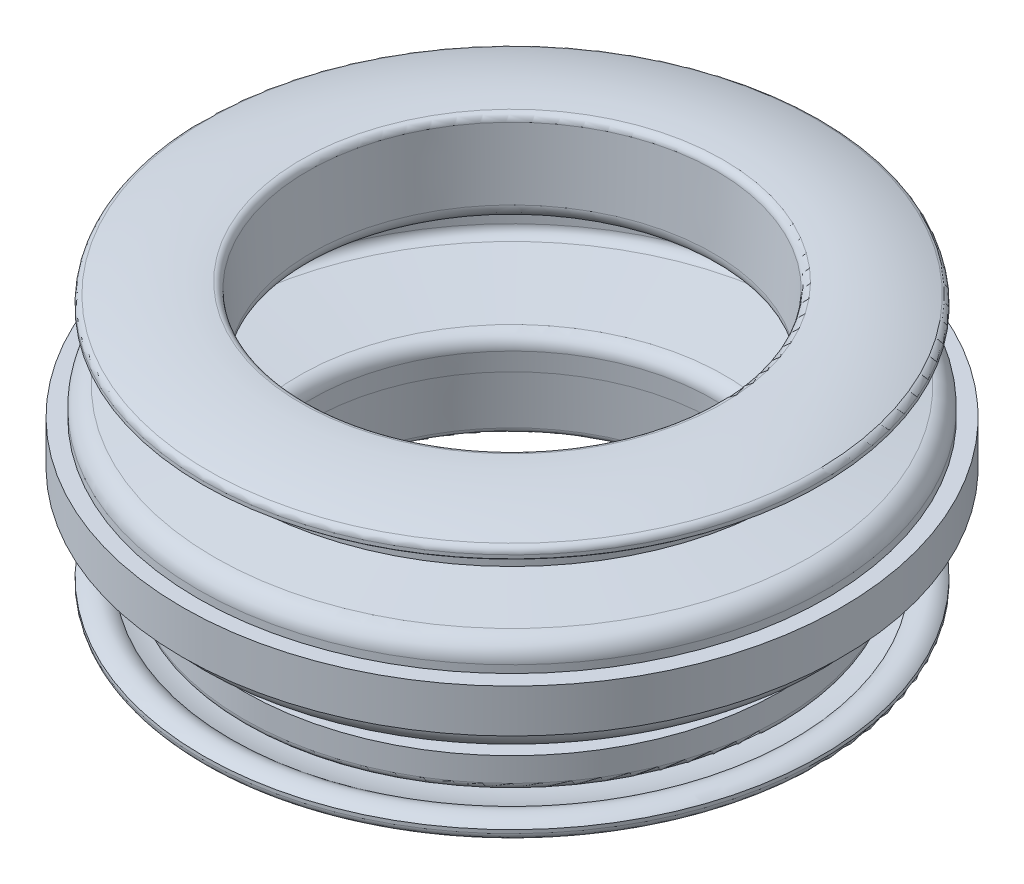
SolidWorks part; units mm, degrees
ref_plane "Front Plane" through (0, 0, 0) normal (0, 0, 1) x (1, 0, 0)
ref_plane "Top Plane" through (0, 0, 0) normal (0, 1, 0) x (1, 0, 0)
ref_plane "Right Plane" through (0, 0, 0) normal (1, 0, 0) x (0, 0, -1)
ref_plane "Plane2" through (0, -4.572, 0) normal (0, 1, 0) x (1, 0, 0)
ref_plane "Plane4" through (0, -45.212, 0) normal (0, 1, 0) x (1, 0, 0)
ref_plane "Plane3" through (0, -24.892, 0) normal (0, 1, 0) x (1, 0, 0)
sketch "Sketch1" plane through (0, 0, 0) normal (0, 0, 1) x (1, 0, 0)
  line L0 (0, 0) -> (0, 51.7671) construction
  line L1 (36.83, 0) -> (36.83, -10.16)
  line L4 (36.83, -10.16) -> (48.26, -10.16)
  line L5 (48.26, -10.16) -> (48.26, -4.572)
  line L6 (48.26, -4.572) -> (43.0459, -4.572)
  line L11 (44.2545, -3.556) -> (39.5655, -3.556) construction
  line L12 (55.5625, -2.286) -> (55.5625, -3.81)
  line L13 (43.0459, -2.54) -> (27.2208, -2.54) construction
  arc A0 (36.83, 0) -> (55.5625, -2.286) centre (41.2472, -41.6979) cw
  arc A1 (43.0459, -2.54) -> (43.0459, -4.572) centre (41.91, -3.556) ccw
  arc A2 (55.5625, -3.81) -> (50.4825, -3.81) centre (53.0225, -0.9702) cw
  arc A3 (43.0459, -2.54) -> (50.4825, -3.81) centre (43.0459, -24.9477) cw
  point P23 (41.91, -3.556)
  dimension "D1" = 73.66
  dimension "D5" = 1.524
  dimension "D2" = 2.032
  dimension "D10" = 41.9312
  dimension "D14" = 3.81
  dimension "D15" = 1.524
  dimension "D3" = 5.08
  dimension "D4" = 96.52
  dimension "D8" = 83.82
  dimension "D9" = 3.556
  dimension "D11" = 111.125
  dimension "D12" = 10.16
  dimension "D16" = 0.762
revolve "Revolve1" add sketch "Sketch1" angle 360 about L0
draft "Draft1" type of draft neutral plane draft angle 3 neutral plane "Top Plane" faces to draft 1 face at (0, -10.16, -36.83) neutral plane through (0, 0, 0) neutral plane normal (0, 1, 0) parameters "D1"=3
fillet "Fillet3" radius 1.27 1 edges at (0, 0, -36.83)
fillet "Fillet4" radius 1.27 1 edges at (0, -2.286, -55.5625)
fillet "Fillet5" radius 1.27 1 edges at (0, -4.572, -48.26)
mirror "Mirror4" about plane through (0, -24.892, 0) normal (0, 1, 0) of bodies 101
sketch "Sketch2" plane through (0, 0, 0) normal (0, 0, 1) x (1, 0, 0)
  line L0 (61.1187, -24.892) -> (-61.1187, -24.892) construction
  line L1 (-59.2604, -24.892) -> (-54.5176, -24.892)
  line L2 (-59.2604, -24.892) -> (-59.2604, -21.0052)
  line L4 (-54.5176, -24.892) -> (-54.5176, -21.0052)
  line L5 (0, 0) -> (0, -56.0151) construction
  line L6 (-54.5176, -21.0052) -> (-54.5176, -20.3326)
  line L7 (-53.0528, -18.6056) -> (-38.2434, -16.1545)
  line L8 (-36.1217, -13.5156) -> (-36.2975, -10.16)
  line L9 (-48.26, -10.16) -> (48.26, -10.16) construction
  line L10 (-36.2975, -10.16) -> (-38.8375, -10.16)
  line L11 (-38.8375, -10.16) -> (-38.8375, -12.0626)
  line L12 (-40.4315, -13.9421) -> (-53.4992, -16.1049)
  line L13 (-56.4949, -19.6371) -> (-56.4949, -21.0052)
  line L15 (-56.4949, -21.0052) -> (-59.2604, -21.0052)
  line L17 (-36.2975, -10.16) -> (36.2975, -10.16) construction
  line L18 (-36.7725, -1.0968) -> (-36.2975, -10.16) construction
  line L19 (-36.7725, -1.0968) -> (36.7725, -1.0968) construction
  arc A0 (-54.5176, -20.3326) -> (-53.0528, -18.6056) centre (-52.767, -20.3326) cw
  arc A1 (-53.4992, -16.1049) -> (-56.4949, -19.6371) centre (-52.9146, -19.6371) ccw
  arc A2 (-38.2434, -16.1545) -> (-36.1217, -13.5156) centre (-38.6582, -13.6486) ccw
  arc A3 (-38.8375, -12.0626) -> (-40.4315, -13.9421) centre (-40.7425, -12.0626) cw
  dimension "D4" = 2.54
  dimension "D5" = 1.905
  dimension "D1" = 109.0351
  dimension "D2" = 3.8868
  dimension "D3" = 4.7429
  dimension "D6" = 2.54
  dimension "D7" = 2.54
revolve "Revolve2" add sketch "Sketch2" angle 360 about L5
mirror "Mirror5" about plane through (0, -24.892, 0) normal (0, 1, 0) of "Revolve2"
